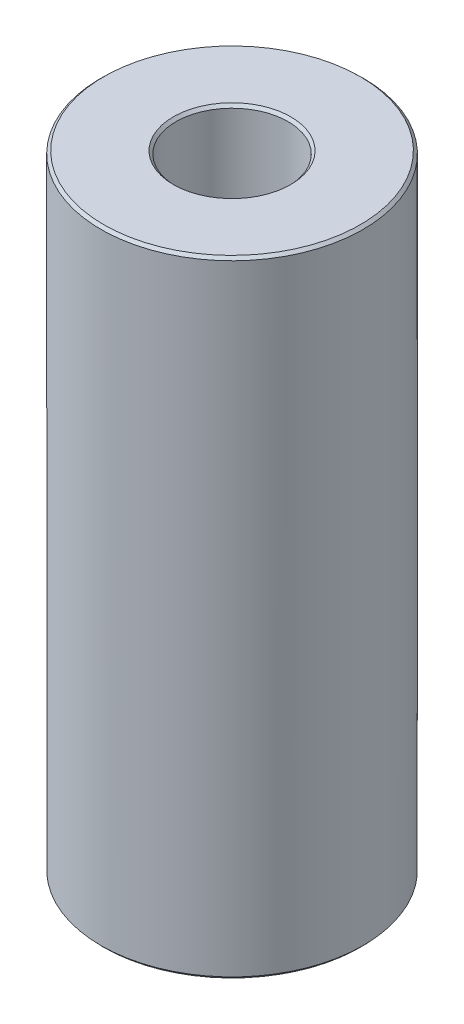
SolidWorks part; units mm, degrees
ref_plane "Front Plane" through (0, 0, 0) normal (0, 0, 1) x (1, 0, 0)
ref_plane "Top Plane" through (0, 0, 0) normal (0, 1, 0) x (1, 0, 0)
ref_plane "Right Plane" through (0, 0, 0) normal (1, 0, 0) x (0, 0, -1)
sketch "Sketch1" plane through (0, 0, 0) normal (0, 1, 0) x (1, 0, 0)
  circle A0 centre (0, 0) radius 60
  dimension "SLEEVE_OD" = 120
extrude "Boss-Extrude1" add sketch "Sketch1" along normal blind 286.399
sketch "Sketch2" plane through (0, 0, 0) normal (0, 1, 0) x (1, 0, 0)
  circle A0 centre (0, 0) radius 25.6578
  dimension "BORE_D" = 51.3156
extrude "Cut-Extrude1" cut sketch "Sketch2" along normal through all
chamfer "Chamfer1" distance 1.2224 angle 46.698 4 edges at (0, 286.399, 25.6578) (0, 0, 25.6578) (0, 0, 60) (0, 286.399, 60) first distance on face at (0, 286.399, 25.6578) first distance on face at (0, 0, 25.6578) first distance on face at (0, 286.399, 60)
